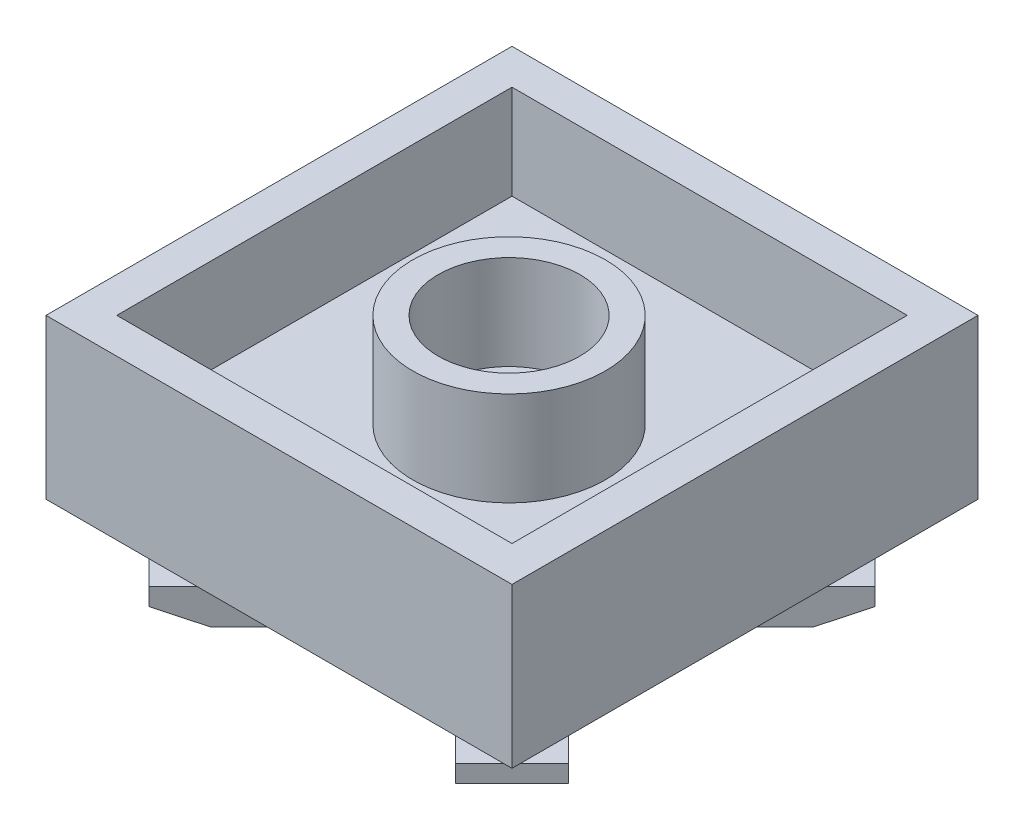
SolidWorks part; units mm, degrees
ref_plane "Front Plane" through (0, 0, 0) normal (0, 0, 1) x (1, 0, 0)
ref_plane "Top Plane" through (0, 0, 0) normal (0, 1, 0) x (1, 0, 0)
ref_plane "Right Plane" through (0, 0, 0) normal (1, 0, 0) x (0, 0, -1)
sketch "Sketch2" plane through (0, 0, 0) normal (0, 1, 0) x (1, 0, 0)
  line L1 (0, 0) -> (15.8, 0)
  line L2 (0, 0) -> (0, 15.8)
  line L3 (0, 15.8) -> (15.8, 15.8)
  line L4 (15.8, 0) -> (15.8, 15.8)
  dimension "D1" = 15.8
  dimension "D2" = 15.8
extrude "Boss-Extrude2" add sketch "Sketch2" against normal blind 5.4
sketch "Sketch4" plane through (0, 0, 0) normal (0, 1, 0) x (1, 0, 0)
  line L0 (15.8, 0) -> (15.8, 15.8) construction
  line L1 (14.6, 14.6) -> (1.2, 14.6)
  line L2 (14.6, 14.6) -> (14.6, 1.2)
  line L3 (14.6, 1.2) -> (1.2, 1.2)
  line L4 (1.2, 14.6) -> (1.2, 1.2)
  line L5 (0, -55) -> (0, 55) construction
  line L6 (-55, 0) -> (55, 0) construction
  line L7 (15.8, 15.8) -> (0, 15.8) construction
  dimension "D1" = 1.2
  dimension "D2" = 1.2
  dimension "D3" = 1.2
  dimension "D4" = 1.2
extrude "Cut-Extrude1" cut sketch "Sketch4" against normal offset from surface (3.2 mm away) 2.2 up to face at (7.9, -5.4, -7.9)
sketch "Sketch7" plane through (0, -3.2, 0) normal (0, 1, 0) x (1, 0, 0)
  line L0 (15.8, 0) -> (15.8, 15.8) construction
  line L1 (15.8, 15.8) -> (0, 15.8) construction
  circle A0 centre (7.85, 7.85) radius 3.265
  circle A1 centre (7.85, 7.85) radius 2.4
  dimension "D1" = 6.53
  dimension "D2" = 4.8
  dimension "D3" = 7.95
  dimension "D4" = 7.95
extrude "Boss-Extrude5" add sketch "Sketch7" along normal up to surface (3.2 mm away) up to face at (7.9, 0, -7.9)
sketch "Sketch8" plane through (0, -5.4, 0) normal (0, -1, 0) x (-1, 0, 0)
  line L0 (-15.8, 0) -> (-15.8, 15.8) construction
  line L1 (-15.8, 15.8) -> (0, 15.8) construction
  circle A0 centre (-7.9, 7.9) radius 5.15
  dimension "D1" = 10.3
  dimension "D2" = 7.9
  dimension "D3" = 7.9
extrude "Cut-Extrude2" cut sketch "Sketch8" against normal blind 0.3
sketch "Sketch11" plane through (0, -5.4, 0) normal (0, -1, 0) x (1, 0, 0)
  line L2 (7.9, -7.9) -> (15.8, 0)
  line L3 (4.51, 0) -> (-4.51, 0) construction
  line L4 (11.683, -2.2078) -> (13.5922, -4.117)
  line L5 (13.5922, -4.117) -> (11.683, -2.2078)
  line L6 (13.5922, -4.117) -> (14.1579, -3.5513)
  line L7 (11.683, -2.2078) -> (12.2487, -1.6421)
  line L8 (14.1579, -3.5513) -> (12.2487, -1.6421)
  line L9 (11.683, -2.2078) -> (10.4597, -3.4311)
  line L10 (13.5922, -4.117) -> (12.3689, -5.3403)
  circle A0 centre (7.9, -7.9) radius 6.7
  circle A1 centre (7.9, -7.9) radius 5.15 construction
  point P9 (12.6376, -3.1624)
  circle M6 centre (7.9, -7.9) radius 5.15
  dimension "D1" = 13.4
  dimension "D2" = 2.7
  dimension "D3" = 0.8
extrude "Boss-Extrude8" add sketch "Sketch11" along normal blind 2.8 contours L2 L8 L7 L4 | A0 L4 L9 | L2 A0 L9 M6 | L10 A0 L2 M6 | A0 L10 L4 | L6 L8 L2 L4 region at (11.5727, -5.4, -3.2684) region at (12.5316, -5.4, -4.2273) region at (12.4432, -5.4, -2.4022) region at (11.8921, -5.4, -2.475) region at (13.3978, -5.4, -3.3568) region at (13.325, -5.4, -3.9079)
ref_axis "Axis1" through (7.9, -5.1, -7.9) along (0, -1, 0)
sketch "Sketch27" plane through (5.3033, 0, 5.3033) normal (0.7071, 0, 0.7071) x (0.7071, 0, -0.7071)
  line L0 (9.8223, -8.2) -> (9.8223, -5.4) construction
  line L1 (12.5223, -8.2) -> (9.8223, -8.2)
  line L2 (12.5223, -8.2) -> (12.5223, -7)
  line L3 (12.5223, -7) -> (9.8223, -7)
  line L4 (9.8223, -8.2) -> (9.8223, -7)
  dimension "D1" = 1.2
extrude "Boss-Extrude10" add sketch "Sketch27" along normal blind 1.2
sketch "Sketch28" plane through (6.9454, 0, -6.9454) normal (-0.7071, 0, 0.7071) x (0.7071, 0, 0.7071)
  line L0 (8.7, -7.6) -> (7.2156, -8.2)
  line L1 (8.7, -7) -> (8.7, -8.2) construction
  line L2 (4.9699, -8.2) -> (8.7, -8.2) construction
  line L3 (7.2156, -8.2) -> (8.7, -8.2)
  line L4 (8.7, -8.2) -> (8.7, -7.6)
extrude "Cut-Extrude3" cut sketch "Sketch28" against normal up to next
pattern_circular "CirPattern1" count 4 over 360 about axis through (7.9, -5.1, -7.9) along (0, -1, 0) of "Boss-Extrude8", "Boss-Extrude10", "Cut-Extrude3"
